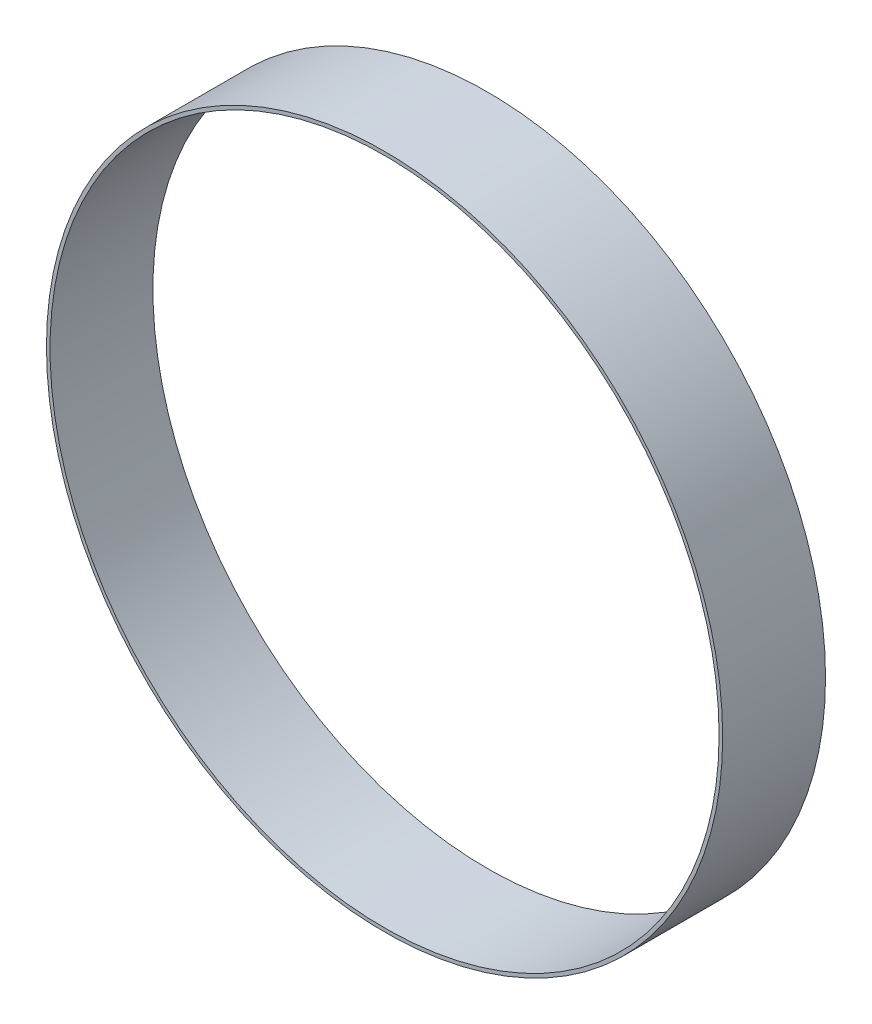
SolidWorks part; units mm, degrees
ref_plane "Plan de face" through (0, 0, 0) normal (0, 0, 1) x (1, 0, 0)
ref_plane "Plan de dessus" through (0, 0, 0) normal (0, 1, 0) x (1, 0, 0)
ref_plane "Plan de droite" through (0, 0, 0) normal (1, 0, 0) x (0, 0, -1)
sketch "Esquisse1" plane through (0, 0, 0) normal (0, 0, 1) x (1, 0, 0)
  circle A0 centre (0, 0) radius 37.4
  circle A1 centre (0, 0) radius 37.8
  dimension "D1" = 74.8
  dimension "D2" = 75.6
extrude "Boss.-Extru.1" add sketch "Esquisse1" along normal blind 11.5
